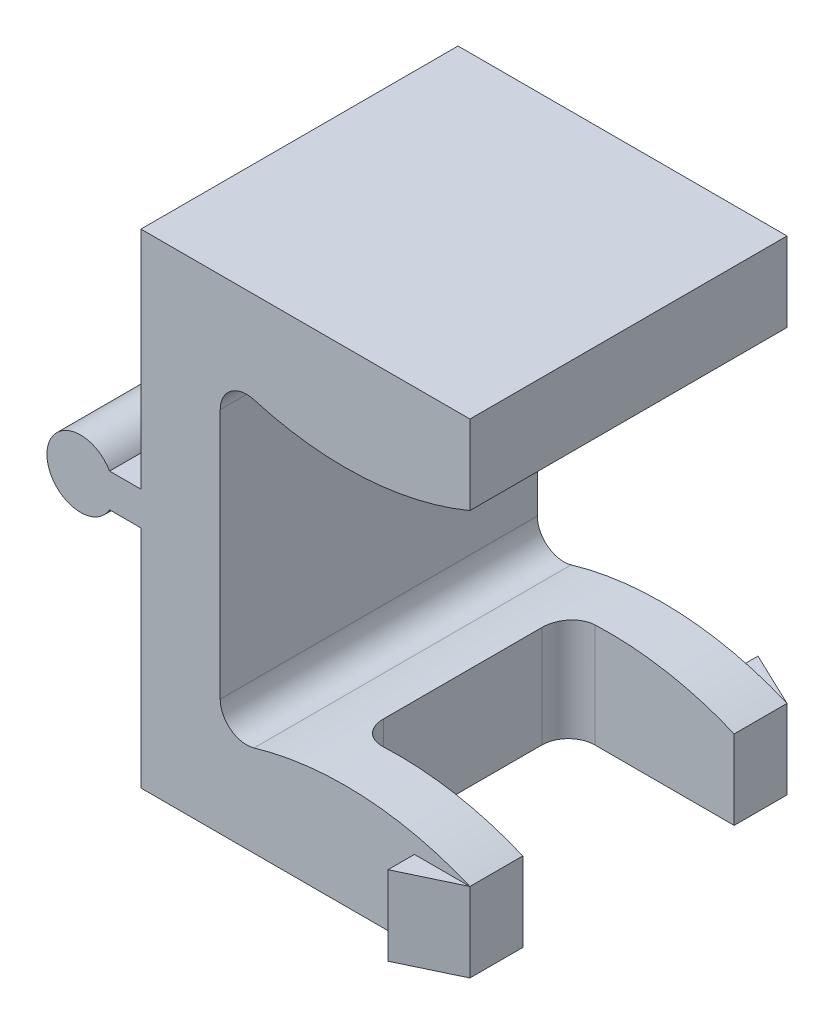
SolidWorks part; units mm, degrees
ref_plane "Front Plane" through (0, 0, 0) normal (0, 0, 1) x (1, 0, 0)
ref_plane "Top Plane" through (0, 0, 0) normal (0, 1, 0) x (1, 0, 0)
ref_plane "Right Plane" through (0, 0, 0) normal (1, 0, 0) x (0, 0, -1)
sketch "Sketch1" plane through (0, 0, 0) normal (0, 0, 1) x (1, 0, 0)
  line L2 (-159.7982, 9.1594) -> (-172.2482, 9.1594)
  line L3 (-172.2482, 9.1594) -> (-172.2482, -9.1594)
  line L7 (-169.2482, -22.8519) -> (-169.2482, 6.1594) construction
  line L12 (-169.2482, 5.1594) -> (-169.2482, 1.9844) construction
  line L13 (-142.8048, 5.1594) -> (-142.8048, -5.1594) construction
  line L15 (-156.5482, 5.1594) -> (21.2518, 5.1594) construction
  line L16 (-156.5482, -5.1594) -> (21.2518, -5.1594) construction
  line L23 (-159.7982, 6.1594) -> (-159.7982, 9.1594)
  line L28 (-164.5232, 5.2094) -> (-144.5007, 5.2094) construction
  line L29 (-156.5482, 5.1594) -> (-169.2482, 5.1594) construction
  line L30 (-169.2482, 6.1594) -> (-169.2482, 5.1594)
  line L34 (-169.2482, 5.1594) -> (-169.2482, -5.1594)
  line L35 (-172.2482, 0) -> (-169.2482, 0) construction
  line L36 (-169.2482, -6.1594) -> (-169.2482, -5.1594)
  line L37 (-159.7982, -6.1594) -> (-159.7982, -9.1594)
  line L38 (-159.7982, -9.1594) -> (-172.2482, -9.1594)
  line L39 (-159.7982, 5.1594) -> (-159.7982, 1.9844) construction
  arc A5 (-169.2482, 6.1594) -> (-159.7982, 6.1594) centre (-164.5232, 17.4347) ccw
  arc A6 (-169.2482, -6.1594) -> (-159.7982, -6.1594) centre (-164.5232, -17.4347) cw
  point P30 (-142.8048, 0)
  dimension "D4" = 3
  dimension "D3" = 3
  dimension "D1" = 0.05
  dimension "D2" = 1
extrude "MainBody" add sketch "Sketch1" along normal mid plane 12
sketch "Sketch3" plane through (0, -9.1594, 0) normal (0, -1, 0) x (1, 0, 0)
  line L0 (-159.7982, -6) -> (-161.8982, -7)
  line L1 (-161.8982, -7) -> (-161.8982, -6)
  line L2 (-172.2482, -6) -> (-159.7982, -6) construction
  line L3 (-161.8982, -6) -> (-159.7982, -6)
  line L4 (-162.8982, -12.7) -> (-162.8982, -6.35) construction
  line L5 (6.8475, 0) -> (-6.8475, 0) construction
  line L6 (-161.8982, 6) -> (-159.7982, 6)
  line L7 (-161.8982, 7) -> (-161.8982, 6)
  line L8 (-159.7982, 6) -> (-161.8982, 7)
  dimension "D1" = 1
  dimension "D2" = 1
extrude "Hook" add sketch "Sketch3" against normal up to vertex (3 mm away) up to point (-159.7982, -6.1594, -6)
sketch "Sketch4" plane through (0, -9.1594, 0) normal (0, -1, 0) x (1, 0, 0)
  line L0 (-159.7982, 6) -> (-159.7982, -6) construction
  line L1 (-159.7982, 4) -> (-166.0732, 4)
  line L2 (-159.7982, 4) -> (-159.7982, -4)
  line L3 (-159.7982, -4) -> (-166.0732, -4)
  line L4 (-166.0732, 4) -> (-166.0732, -4)
  line L5 (-172.2482, 6) -> (-172.2482, -6) construction
  line L6 (-172.2482, -6) -> (-161.8982, -6) construction
  line L7 (-162.8982, -6.35) -> (-169.2482, -6.35) construction
  point P6 (-166.0732, 0)
  point P9 (-172.2482, 0)
  point P14 (-166.0732, -6.35)
  dimension "D1" = 2
extrude "Flex" cut sketch "Sketch4" against normal up to next
fillet "Fillet1" radius 1 2 edges at (-166.0732, -7.2337, -4) (-166.0732, -7.2337, 4)
fillet "Fillet2" radius 1 2 edges at (-169.2482, 6.1594, 0) (-169.2482, -6.1594, 0)
sketch "Sketch5" [suppressed] plane through (-172.2482, 0, 0) normal (-1, 0, 0) x (0, 0, 1)
  line L1 (-6, 9.1594) -> (6, 9.1594)
  line L2 (-6, 9.1594) -> (-6, -9.1594)
  line L3 (-6, -9.1594) -> (6, -9.1594)
  line L4 (6, 9.1594) -> (6, -9.1594)
extrude "Boss-Extrude1" [suppressed] add sketch "Sketch5" along normal blind 15
sketch "Sketch6" [suppressed] plane through (0, 9.1594, 0) normal (0, 1, 0) x (1, 0, 0)
  line L0 (-187.2482, -6) -> (-187.2482, 6) construction
  circle A0 centre (-182.2482, 0) radius 3.302
  dimension "D1" = 6.604
  dimension "D2" = 5
extrude "Cut-Extrude2" [suppressed] cut sketch "Sketch6" against normal through all
sketch "Sketch7" plane through (-172.2482, 0, 0) normal (-1, 0, 0) x (0, 0, 1)
  circle A0 centre (0, 0) radius 38.1
  dimension "D1" = 76.2
extrude "Boss-Extrude2" [suppressed] add sketch "Sketch7" along normal blind 5
fillet "Fillet3" [suppressed] radius 1
sketch "Sketch8" plane through (0, 0, 6) normal (0, 0, 1) x (1, 0, 0)
  line L6 (-172.2482, -0.635) -> (-173.4343, -0.635)
  line L8 (-172.2482, 0.635) -> (-173.4343, 0.635)
  line L10 (-172.2482, 0.635) -> (-173.4343, 0.635)
  line L11 (-172.2482, 0.635) -> (-172.2482, -0.635)
  line L12 (-161.8982, -9.1594) -> (-161.8982, -6.1594)
  line L13 (-161.8982, -6.1594) -> (-159.7982, -6.1594)
  line L14 (-169.2482, -4.7448) -> (-169.2482, 4.7448)
  line L15 (-159.7982, 6.1594) -> (-159.7982, 9.1594)
  line L16 (-159.7982, 9.1594) -> (-172.2482, 9.1594)
  line L17 (-172.2482, 9.1594) -> (-172.2482, -9.1594)
  line L18 (-172.2482, -9.1594) -> (-161.8982, -9.1594)
  line L19 (-161.8982, -9.1594) -> (-161.8982, -6.1594)
  line L20 (-161.8982, -6.1594) -> (-159.7982, -6.1594)
  line L21 (-169.2482, -4.7448) -> (-169.2482, 4.7448)
  line L22 (-159.7982, 6.1594) -> (-159.7982, 9.1594)
  line L23 (-159.7982, 9.1594) -> (-172.2482, 9.1594)
  line L24 (-172.2482, 9.1594) -> (-172.2482, -9.1594)
  line L25 (-172.2482, -9.1594) -> (-161.8982, -9.1594)
  line L26 (-172.2482, -0.635) -> (-173.4343, -0.635)
  arc A0 (-173.4343, 0.635) -> (-173.4343, -0.635) centre (-174.5342, 0) ccw
  arc A4 (-159.7982, -6.1594) -> (-167.9665, -5.7043) centre (-164.5232, -17.4347) ccw
  arc A5 (-169.2482, -4.7448) -> (-167.9665, -5.7043) centre (-168.2482, -4.7448) ccw
  arc A6 (-167.9665, 5.7043) -> (-169.2482, 4.7448) centre (-168.2482, 4.7448) ccw
  arc A7 (-167.9665, 5.7043) -> (-159.7982, 6.1594) centre (-164.5232, 17.4347) ccw
  arc A8 (-159.7982, -6.1594) -> (-167.9665, -5.7043) centre (-164.5232, -17.4347) ccw
  arc A9 (-169.2482, -4.7448) -> (-167.9665, -5.7043) centre (-168.2482, -4.7448) ccw
  arc A10 (-167.9665, 5.7043) -> (-169.2482, 4.7448) centre (-168.2482, 4.7448) ccw
  arc A11 (-167.9665, 5.7043) -> (-159.7982, 6.1594) centre (-164.5232, 17.4347) ccw
  point P6 (-172.2482, 0)
  line M14 (-172.2482, 9.1594) -> (-172.2482, -9.1594)
  dimension "D2" = 1.27
  dimension "D1" = 0
  dimension "D3" = 2.286
extrude "Slot" add sketch "Sketch8" against normal up to surface (12 mm away) contours L8 A0 L6 M14 region at (-174.164, 0, 6) up to face at (-165.6835, -0.5599, -6)
equation "\"HookThickness\"= 3mm"
equation "\"D3@Sketch1\"=\"HookThickness\""
equation "\"D4@Sketch1\"=\"HookThickness\""
equation "\"CylinderDiameter\"=3"
equation "\"D1@Sketch7\"=\"CylinderDiameter\""
